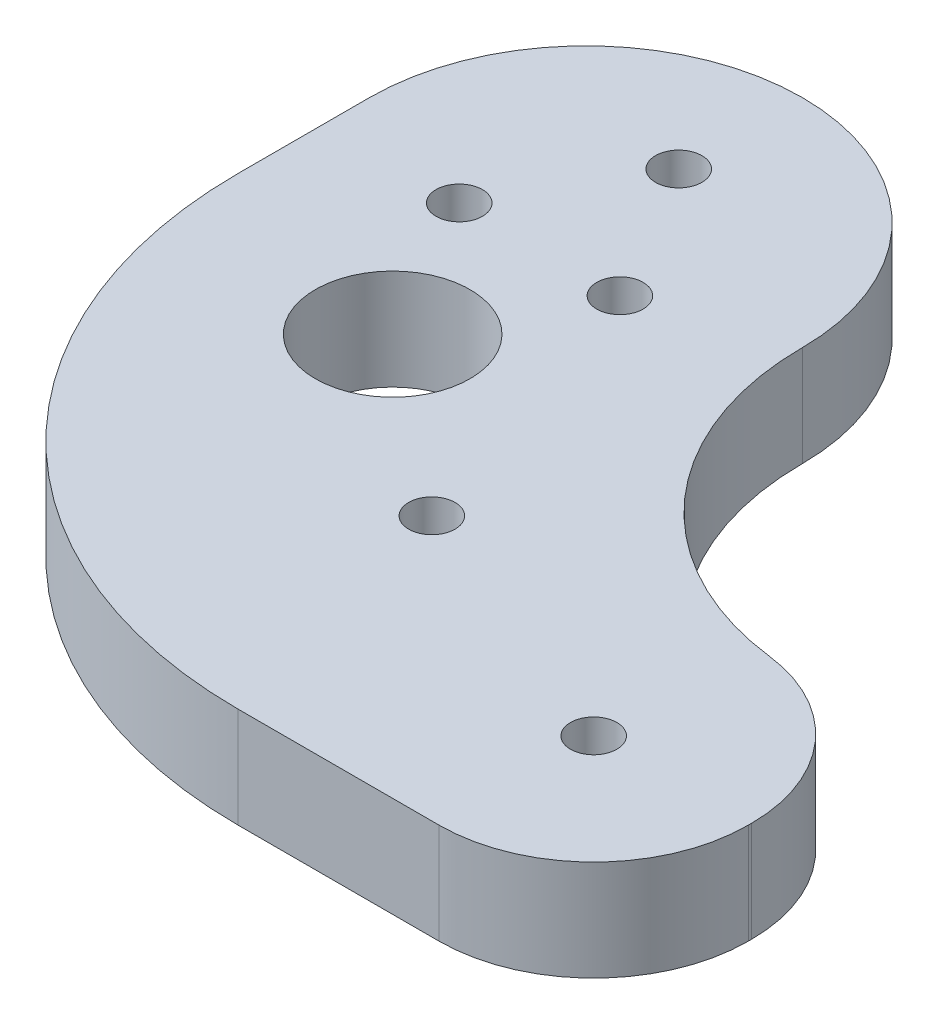
SolidWorks part; units mm, degrees
ref_plane "前视基准面" through (0, 0, 0) normal (0, 0, 1) x (1, 0, 0)
ref_plane "上视基准面" through (0, 0, 0) normal (0, 1, 0) x (1, 0, 0)
ref_plane "右视基准面" through (0, 0, 0) normal (1, 0, 0) x (0, 0, -1)
sketch "草图1" plane through (0, 0, 0) normal (0, 1, 0) x (1, 0, 0)
  line L0 (0, 0) -> (53, 0)
  line L1 (0, 38.5) -> (0, 0)
  line L2 (19.1962, 35.5) -> (43, 10) construction
  line L3 (31.0981, 22.75) -> (25.4412, 17.0931) construction
  line L5 (53, 0) -> (53, 20)
  line L6 (53, 20) -> (46.5, 20)
  arc A0 (28, 38.5) -> (46.5, 20) centre (46.5, 38.5) ccw
  arc A1 (28, 38.5) -> (0, 38.5) centre (14, 38.5) ccw
  circle A2 centre (14, 38.5) radius 6 construction
  circle A3 centre (14, 44.5) radius 1.5
  circle A4 centre (19.1962, 35.5) radius 1.5
  circle A6 centre (43, 10) radius 1.5
  circle A7 centre (14, 26) radius 5
  circle A8 centre (8.8038, 35.5) radius 1.5
  circle A9 centre (25.4412, 17.0931) radius 1.5
  point P25 (14, 38.5)
  dimension "D1" = 10
  dimension "D3" = 3
  dimension "D4" = 12
  dimension "D5" = 3
  dimension "D6" = 10
  dimension "D7" = 53
  dimension "D9" = 14
  dimension "D10" = 18.5
  dimension "D15" = 3
  dimension "D16" = 6.5
  dimension "D17" = 8
  dimension "D12" = 10
  dimension "D8" = 38.5
  dimension "D11" = 20
  dimension "D13" = 14
  dimension "D14" = 3
  dimension "D18" = 12.5
extrude "凸台-拉伸1" add sketch "草图1" along normal blind 3.5
extrude "凸台-拉伸2" add sketch "草图1<2>" along normal blind 6.5
sketch "草图1<2>" plane through (0, 0, 0) normal (0, 1, 0) x (1, 0, 0) same geometry as "草图1"
fillet "圆角3" radius 10 1 edges at (53, 3.25, 0)
fillet "圆角4" radius 10 1 edges at (53, 3.25, -20)
fillet "圆角5" radius 30 1 edges at (0, 3.25, 0)
